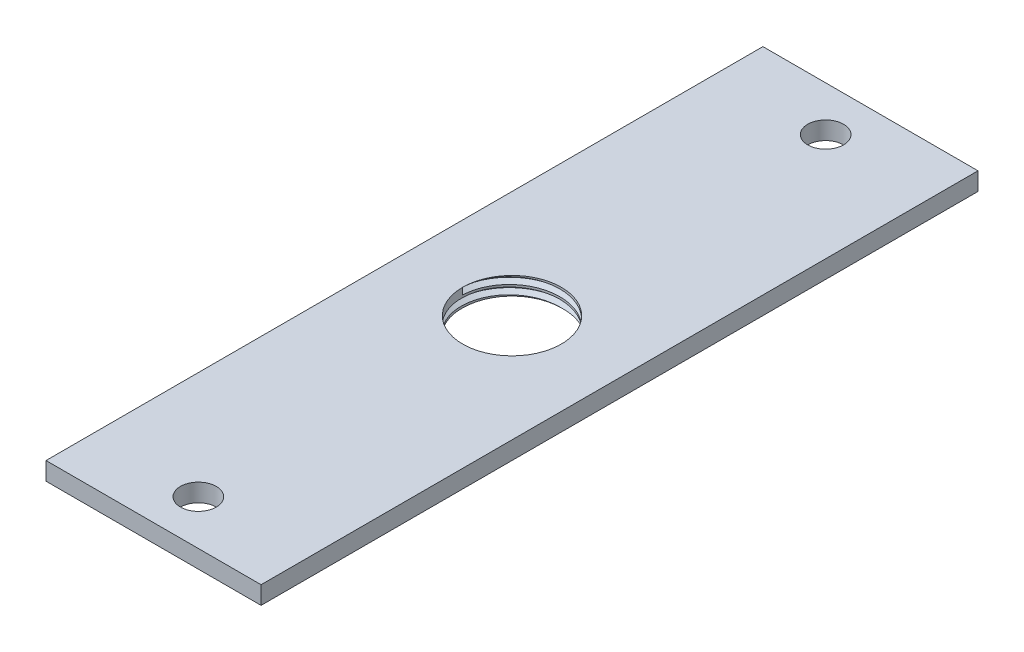
SolidWorks part; units mm, degrees
material "6061-T6 (SS)"
ref_plane "Front Plane" through (0, 0, 0) normal (0, 0, 1) x (1, 0, 0)
ref_plane "Top Plane" through (0, 0, 0) normal (0, 1, 0) x (1, 0, 0)
ref_plane "Right Plane" through (0, 0, 0) normal (1, 0, 0) x (0, 0, -1)
sketch "Sketch1" plane through (0, 0, 0) normal (0, 1, 0) x (1, 0, 0)
  line L1 (-17.653, -47.498) -> (17.653, -47.498) construction
  line L2 (-17.653, -47.498) -> (-17.653, 47.498) construction
  line L3 (-17.653, 47.498) -> (17.653, 47.498) construction
  line L4 (17.653, -47.498) -> (17.653, 47.498) construction
  line L5 (-17.653, -47.498) -> (17.653, 47.498) construction
  line L6 (-17.653, 47.498) -> (17.653, -47.498) construction
  line L7 (-19.05, -63.5) -> (19.05, -63.5)
  line L8 (-19.05, -63.5) -> (-19.05, 63.5)
  line L9 (-19.05, 63.5) -> (19.05, 63.5)
  line L10 (19.05, -63.5) -> (19.05, 63.5)
  line L11 (-19.05, -63.5) -> (19.05, 63.5) construction
  line L12 (-19.05, 63.5) -> (19.05, -63.5) construction
  point P0 (0, 0)
  point P6 (0, 0)
  dimension "D1" = 35.306
  dimension "D2" = 94.996
  dimension "D3" = 38.1
  dimension "D4" = 127
extrude "Boss-Extrude1" add sketch "Sketch1" along normal mid plane 3.175
sketch "Sketch2" plane through (0, 1.5875, 0) normal (0, 1, 0) x (1, 0, 0)
  circle A0 centre (0, 0) radius 8.7312
  dimension "D1" = 17.4625
extrude "Cut-Extrude1" cut sketch "Sketch2" against normal blind 19.05
sketch "Sketch3" plane through (0, 1.5875, 0) normal (0, 1, 0) x (1, 0, 0)
  line L0 (-77.5848, 0) -> (77.5848, 0) construction
  line L1 (0, -73.9996) -> (0, 73.9996) construction
  line L2 (19.05, 63.5) -> (-19.05, 63.5) construction
  circle A0 centre (0, 55.5625) radius 3.175
  circle A1 centre (0, -55.5625) radius 3.175
  point P5 (0, 0)
  point P9 (0, 0)
  dimension "D1" = 7.9375
  dimension "D2" = 6.35
extrude "Cut-Extrude2" cut sketch "Sketch3" against normal blind 3.175
thread "Thread1" pitch 1.5875 method cut profile "Thread Profile1" start angle 0, offset 0, length 0, pitch 1.5875, diameter 17.4625
ref_plane "Plane1" through (-8.7312, 1.5875, 0) normal (0, 0, 1) x (-1, 0, 0)
sketch "Thread Profile1" plane through (-8.7312, 1.5875, 0) normal (0, 0, 1) x (-1, 0, 0)
  line L0 (0, 0) -> (0, 1.5875) construction
  line L1 (0, 0) -> (0.8593, 0.4961)
  line L2 (0.8593, 0.4961) -> (0.8593, 0.6945)
  line L3 (0.8593, 0.6945) -> (0, 1.1906)
  line L4 (0.8593, 0.5953) -> (0, 0.5953) construction
  line L11 (0, 0) -> (0, 1.1906)
  point P2 (0, 0)
  dimension "Pitch" = 1.5875
  dimension "Profile_Angle" = 60
  dimension "Profile_Land" = 0.1984
  dimension "Profile_Height" = 0.8593
